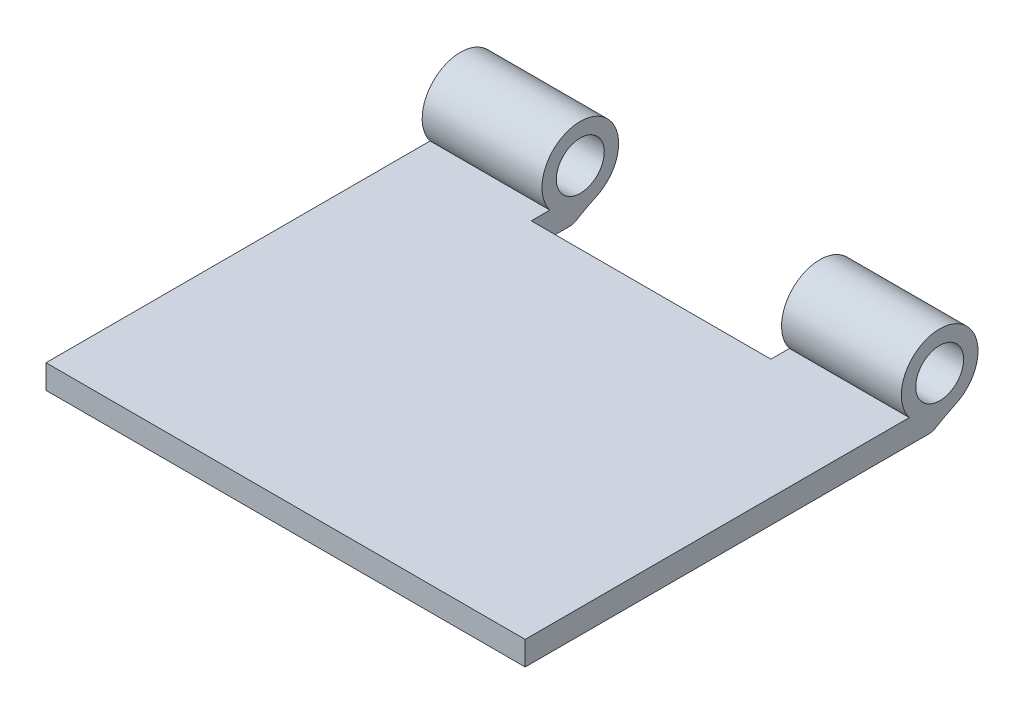
SolidWorks part; units mm, degrees
ref_plane "Front Plane" through (0, 0, 0) normal (0, 0, 1) x (1, 0, 0)
ref_plane "Top Plane" through (0, 0, 0) normal (0, 1, 0) x (1, 0, 0)
ref_plane "Right Plane" through (0, 0, 0) normal (1, 0, 0) x (0, 0, -1)
sketch "Sketch1" plane through (0, 0, 0) normal (0, 1, 0) x (1, 0, 0)
  line L1 (-10, 8.5) -> (10, 8.5)
  line L2 (-10, 8.5) -> (-10, -8.5)
  line L3 (-10, -8.5) -> (10, -8.5)
  line L4 (10, 8.5) -> (10, -8.5)
  line L5 (-10, 8.5) -> (10, -8.5) construction
  line L6 (-10, -8.5) -> (10, 8.5) construction
  point P0 (0, 0)
extrude "Boss-Extrude1" add sketch "Sketch1" along normal blind 1
sketch "Sketch2" plane through (10, 0, 0) normal (1, 0, 0) x (0, 0, -1)
  circle A0 centre (8.8004, 1.9744) radius 1
  circle A1 centre (8.8004, 1.9744) radius 1.6
extrude "Boss-Extrude2" add sketch "Sketch2" against normal up to vertex (20 mm away) up to point (-10, 1, -8.5)
fillet "Fillet1" radius 10 1 edges at (0, 0.4029, -8.5)
fillet "Fillet2" radius 0.5 1 edges at (0, 0, -8.5)
sketch "Sketch4" plane through (0, 0, 0) normal (0, 1, 0) x (1, 0, 0)
  line L1 (-5, 16.8599) -> (5, 16.8599)
  line L2 (-5, 16.8599) -> (-5, 6.7551)
  line L3 (-5, 6.7551) -> (5, 6.7551)
  line L4 (5, 16.8599) -> (5, 6.7551)
  line L5 (-5, 16.8599) -> (5, 6.7551) construction
  line L6 (-5, 6.7551) -> (5, 16.8599) construction
  point P0 (0, 11.8075)
extrude "Cut-Extrude3" cut sketch "Sketch4" along normal through all
